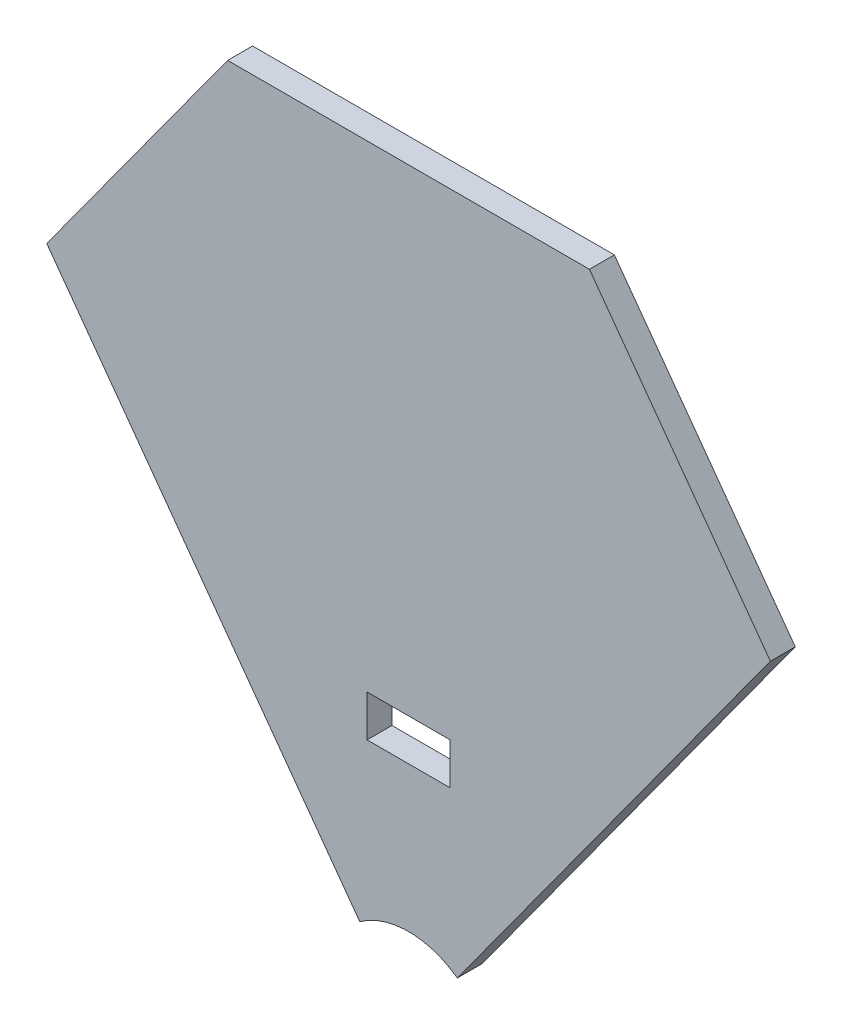
SolidWorks part; units mm, degrees
ref_plane "Front Plane" through (0, 0, 0) normal (0, 0, 1) x (1, 0, 0)
ref_plane "Top Plane" through (0, 0, 0) normal (0, 1, 0) x (1, 0, 0)
ref_plane "Right Plane" through (0, 0, 0) normal (1, 0, 0) x (0, 0, -1)
sketch "Sketch3" plane through (0, 0, 0) normal (0, 0, 1) x (1, 0, 0)
  line L0 (0, 0) -> (54.4907, 75)
  line L1 (54.4907, 75) -> (-54.4907, 75)
  line L2 (-54.4907, 75) -> (0, 0)
  line L4 (-5, 32.5) -> (5, 32.5)
  line L5 (-5, 32.5) -> (-5, 27.5)
  line L6 (-5, 27.5) -> (5, 27.5)
  line L7 (5, 32.5) -> (5, 27.5)
  point P5 (0, 75)
  point P9 (0, 0)
  point P10 (0, 27.5)
  point P11 (5, 30)
  dimension "D1" = 72
  dimension "D2" = 75
  dimension "D3" = 10
  dimension "D4" = 5
  dimension "D5" = 30
extrude "Boss-Extrude1" add sketch "Sketch3" along normal blind 3
ref_plane "Offset_R" through (0, 75, 0) normal (0, 1, 0) x (1, 0, 0)
sketch "Sketch4" plane through (0, 0, 0) normal (0, 0, -1) x (-1, 0, 0)
  line L0 (-54.4907, 75) -> (-65.3888, 90)
  line L1 (-65.3888, 90) -> (65.3888, 90)
  line L2 (65.3888, 90) -> (54.4907, 75)
  line L3 (54.4907, 75) -> (-54.4907, 75)
  line L4 (0, 0) -> (-54.4907, 75) construction
  line L5 (54.4907, 75) -> (0, 0) construction
  dimension "D1" = 15
extrude "Boss-Extrude2" add sketch "Sketch4" against normal up to surface (3 mm away) up to face at (0, 50, 3)
sketch "Sketch5" plane through (0, 0, 3) normal (0, 0, 1) x (1, 0, 0)
  line L0 (-65.3888, 90) -> (-21.7963, 90)
  line L1 (-65.3888, 90) -> (65.3888, 90) construction
  line L2 (-21.7963, 90) -> (-43.5926, 60)
  line L3 (-65.3888, 90) -> (0, 0) construction
  line L4 (-43.5926, 60) -> (-65.3888, 90)
  line L5 (65.3888, 90) -> (21.7963, 90)
  line L6 (21.7963, 90) -> (43.5926, 60)
  line L7 (0, 0) -> (65.3888, 90) construction
  line L8 (43.5926, 60) -> (65.3888, 90)
  dimension "D1" = 30
extrude "Cut-Extrude1" cut sketch "Sketch5" against normal through all
ref_axis "Axis1" through (0, 0, 10.9079) along (0, 0, -1)
sketch "Sketch6" plane through (0, 0, 0) normal (0, 0, -1) x (-1, 0, 0)
  circle A0 centre (0, 0) radius 10
extrude "Cut-Extrude2" cut sketch "Sketch6" against normal through all
